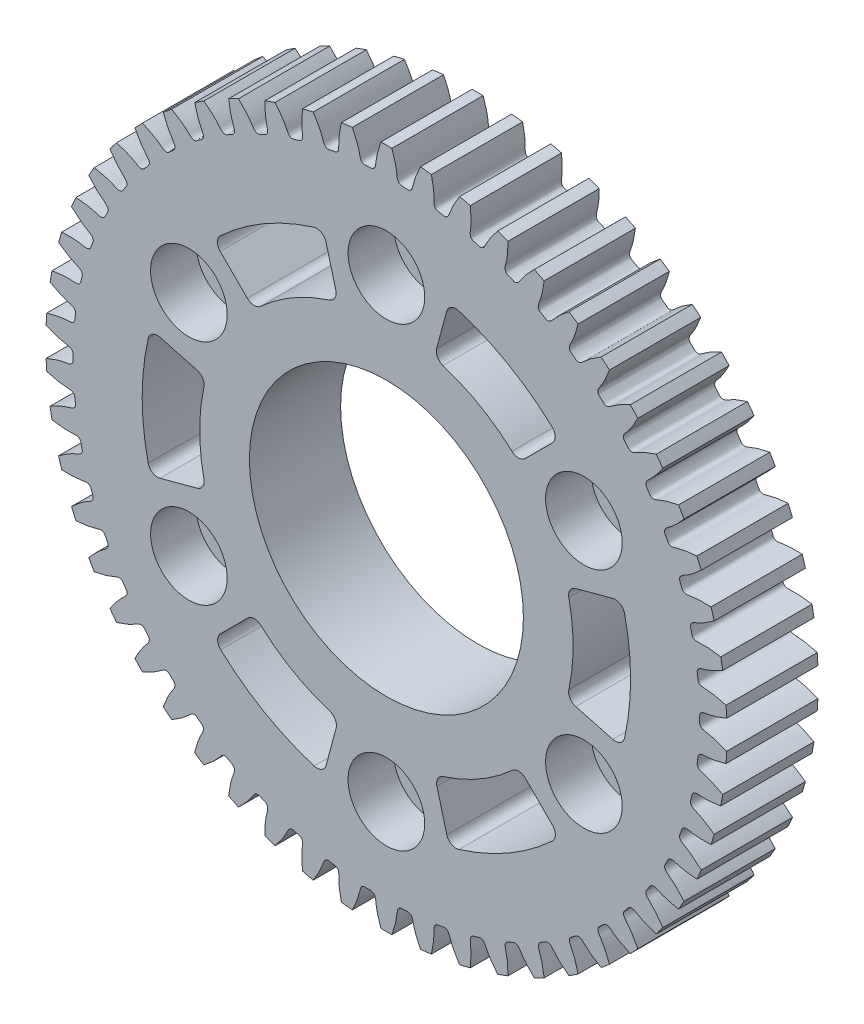
SolidWorks part; units mm, degrees
ref_plane "Front Plane" through (0, 0, 0) normal (0, 0, 1) x (1, 0, 0)
ref_plane "Top Plane" through (0, 0, 0) normal (0, 1, 0) x (1, 0, 0)
ref_plane "Right Plane" through (0, 0, 0) normal (1, 0, 0) x (0, 0, -1)
ref_plane "Plane1" through (0, 0, 4.7625) normal (0, 0, 1) x (1, 0, 0)
sketch "Sketch1" plane through (0, 0, 4.7625) normal (0, 0, 1) x (1, 0, 0)
  arc A0 (35.1151, 5.6076) -> (34.9153, 6.7406) centre (0, 0) ccw
  arc A1 (34.2266, 9.6463) -> (33.8967, 10.7484) centre (0, 0) ccw
  arc A2 (32.8753, 13.5546) -> (32.4197, 14.6109) centre (0, 0) ccw
  arc A3 (31.0794, 17.2795) -> (30.5042, 18.2758) centre (0, 0) ccw
  arc A4 (28.8633, 20.7708) -> (28.1763, 21.6936) centre (0, 0) ccw
  arc A5 (26.2568, 23.9812) -> (25.4673, 24.818) centre (0, 0) ccw
  arc A6 (23.2952, 26.8672) -> (22.4139, 27.6067) centre (0, 0) ccw
  arc A7 (20.0186, 29.39) -> (19.0574, 30.0221) centre (0, 0) ccw
  arc A8 (16.4712, 31.5153) -> (15.4432, 32.0316) centre (0, 0) ccw
  arc A9 (12.7012, 33.2144) -> (11.6201, 33.6078) centre (0, 0) ccw
  arc A10 (8.7593, 34.4643) -> (7.6399, 34.7296) centre (0, 0) ccw
  arc A11 (4.6991, 35.2482) -> (3.5564, 35.3817) centre (0, 0) ccw
  arc A12 (0.5752, 35.5553) -> (-0.5752, 35.5553) centre (0, 0) ccw
  arc A13 (-3.5564, 35.3817) -> (-4.6991, 35.2482) centre (0, 0) ccw
  arc A14 (-7.6399, 34.7296) -> (-8.7593, 34.4643) centre (0, 0) ccw
  arc A15 (-11.6201, 33.6078) -> (-12.7012, 33.2144) centre (0, 0) ccw
  arc A16 (-15.4432, 32.0316) -> (-16.4712, 31.5153) centre (0, 0) ccw
  arc A17 (-19.0574, 30.0221) -> (-20.0186, 29.39) centre (0, 0) ccw
  arc A18 (-22.4139, 27.6067) -> (-23.2952, 26.8672) centre (0, 0) ccw
  arc A19 (-25.4673, 24.818) -> (-26.2568, 23.9812) centre (0, 0) ccw
  arc A20 (-28.1763, 21.6936) -> (-28.8633, 20.7708) centre (0, 0) ccw
  arc A21 (-30.5042, 18.2758) -> (-31.0794, 17.2795) centre (0, 0) ccw
  arc A22 (-32.4197, 14.6109) -> (-32.8753, 13.5546) centre (0, 0) ccw
  arc A23 (-33.8967, 10.7484) -> (-34.2266, 9.6463) centre (0, 0) ccw
  arc A24 (-34.9153, 6.7406) -> (-35.1151, 5.6076) centre (0, 0) ccw
  arc A25 (-35.4617, 2.6416) -> (-35.5286, 1.4931) centre (0, 0) ccw
  arc A26 (-35.5286, -1.4931) -> (-35.4617, -2.6416) centre (0, 0) ccw
  arc A27 (-35.1151, -5.6076) -> (-34.9153, -6.7406) centre (0, 0) ccw
  arc A28 (-34.2266, -9.6463) -> (-33.8967, -10.7484) centre (0, 0) ccw
  arc A29 (-32.8753, -13.5546) -> (-32.4197, -14.6109) centre (0, 0) ccw
  arc A30 (-31.0794, -17.2795) -> (-30.5042, -18.2758) centre (0, 0) ccw
  arc A31 (-28.8633, -20.7708) -> (-28.1763, -21.6936) centre (0, 0) ccw
  arc A32 (-26.2568, -23.9812) -> (-25.4673, -24.818) centre (0, 0) ccw
  arc A33 (-23.2952, -26.8672) -> (-22.4139, -27.6067) centre (0, 0) ccw
  arc A34 (-20.0186, -29.39) -> (-19.0574, -30.0221) centre (0, 0) ccw
  arc A35 (-16.4712, -31.5153) -> (-15.4432, -32.0316) centre (0, 0) ccw
  arc A36 (-12.7012, -33.2144) -> (-11.6201, -33.6078) centre (0, 0) ccw
  arc A37 (-8.7593, -34.4643) -> (-7.6399, -34.7296) centre (0, 0) ccw
  arc A38 (-4.6991, -35.2482) -> (-3.5564, -35.3817) centre (0, 0) ccw
  arc A39 (-0.5752, -35.5553) -> (0.5752, -35.5553) centre (0, 0) ccw
  arc A40 (3.5564, -35.3817) -> (4.6991, -35.2482) centre (0, 0) ccw
  arc A41 (7.6399, -34.7296) -> (8.7593, -34.4643) centre (0, 0) ccw
  arc A42 (11.6201, -33.6078) -> (12.7012, -33.2144) centre (0, 0) ccw
  arc A43 (15.4432, -32.0316) -> (16.4712, -31.5153) centre (0, 0) ccw
  arc A44 (19.0574, -30.0221) -> (20.0186, -29.39) centre (0, 0) ccw
  arc A45 (22.4139, -27.6067) -> (23.2952, -26.8672) centre (0, 0) ccw
  arc A46 (25.4673, -24.818) -> (26.2568, -23.9812) centre (0, 0) ccw
  arc A47 (28.1763, -21.6936) -> (28.8633, -20.7708) centre (0, 0) ccw
  arc A48 (30.5042, -18.2758) -> (31.0794, -17.2795) centre (0, 0) ccw
  arc A49 (32.4197, -14.6109) -> (32.8753, -13.5546) centre (0, 0) ccw
  arc A50 (33.8967, -10.7484) -> (34.2266, -9.6463) centre (0, 0) ccw
  arc A51 (34.9153, -6.7406) -> (35.1151, -5.6076) centre (0, 0) ccw
  arc A52 (35.4617, -2.6416) -> (35.5286, -1.4931) centre (0, 0) ccw
  arc A53 (35.5286, 1.4931) -> (35.4617, 2.6416) centre (0, 0) ccw
  spline S0 degree 3 number of poles 69 (35.4617, 2.6416) -> (35.1151, 5.6076)
  spline S1 degree 3 number of poles 69 (34.9153, 6.7406) -> (34.2266, 9.6463)
  spline S2 degree 3 number of poles 69 (33.8967, 10.7484) -> (32.8753, 13.5546)
  spline S3 degree 3 number of poles 69 (32.4197, 14.6109) -> (31.0794, 17.2795)
  spline S4 degree 3 number of poles 69 (30.5042, 18.2758) -> (28.8633, 20.7708)
  spline S5 degree 3 number of poles 69 (28.1763, 21.6936) -> (26.2568, 23.9812)
  spline S6 degree 3 number of poles 69 (25.4673, 24.818) -> (23.2952, 26.8672)
  spline S7 degree 3 number of poles 69 (22.4139, 27.6067) -> (20.0186, 29.39)
  spline S8 degree 3 number of poles 69 (19.0574, 30.0221) -> (16.4712, 31.5153)
  spline S9 degree 3 number of poles 69 (15.4432, 32.0316) -> (12.7012, 33.2144)
  spline S10 degree 3 number of poles 69 (11.6201, 33.6078) -> (8.7593, 34.4643)
  spline S11 degree 3 number of poles 69 (7.6399, 34.7296) -> (4.6991, 35.2482)
  spline S12 degree 3 number of poles 69 (3.5564, 35.3817) -> (0.5752, 35.5553)
  spline S13 degree 3 number of poles 69 (-0.5752, 35.5553) -> (-3.5564, 35.3817)
  spline S14 degree 3 number of poles 69 (-4.6991, 35.2482) -> (-7.6399, 34.7296)
  spline S15 degree 3 number of poles 69 (-8.7593, 34.4643) -> (-11.6201, 33.6078)
  spline S16 degree 3 number of poles 69 (-12.7012, 33.2144) -> (-15.4432, 32.0316)
  spline S17 degree 3 number of poles 69 (-16.4712, 31.5153) -> (-19.0574, 30.0221)
  spline S18 degree 3 number of poles 69 (-20.0186, 29.39) -> (-22.4139, 27.6067)
  spline S19 degree 3 number of poles 69 (-23.2952, 26.8672) -> (-25.4673, 24.818)
  spline S20 degree 3 number of poles 69 (-26.2568, 23.9812) -> (-28.1763, 21.6936)
  spline S21 degree 3 number of poles 69 (-28.8633, 20.7708) -> (-30.5042, 18.2758)
  spline S22 degree 3 number of poles 69 (-31.0794, 17.2795) -> (-32.4197, 14.6109)
  spline S23 degree 3 number of poles 69 (-32.8753, 13.5546) -> (-33.8967, 10.7484)
  spline S24 degree 3 number of poles 69 (-34.2266, 9.6463) -> (-34.9153, 6.7406)
  spline S25 degree 3 number of poles 69 (-35.1151, 5.6076) -> (-35.4617, 2.6416)
  spline S26 degree 3 number of poles 69 (-35.5286, 1.4931) -> (-35.5286, -1.4931)
  spline S27 degree 3 number of poles 69 (-35.4617, -2.6416) -> (-35.1151, -5.6076)
  spline S28 degree 3 number of poles 69 (-34.9153, -6.7406) -> (-34.2266, -9.6463)
  spline S29 degree 3 number of poles 69 (-33.8967, -10.7484) -> (-32.8753, -13.5546)
  spline S30 degree 3 number of poles 69 (-32.4197, -14.6109) -> (-31.0794, -17.2795)
  spline S31 degree 3 number of poles 69 (-30.5042, -18.2758) -> (-28.8633, -20.7708)
  spline S32 degree 3 number of poles 69 (-28.1763, -21.6936) -> (-26.2568, -23.9812)
  spline S33 degree 3 number of poles 69 (-25.4673, -24.818) -> (-23.2952, -26.8672)
  spline S34 degree 3 number of poles 69 (-22.4139, -27.6067) -> (-20.0186, -29.39)
  spline S35 degree 3 number of poles 69 (-19.0574, -30.0221) -> (-16.4712, -31.5153)
  spline S36 degree 3 number of poles 69 (-15.4432, -32.0316) -> (-12.7012, -33.2144)
  spline S37 degree 3 number of poles 69 (-11.6201, -33.6078) -> (-8.7593, -34.4643)
  spline S38 degree 3 number of poles 69 (-7.6399, -34.7296) -> (-4.6991, -35.2482)
  spline S39 degree 3 number of poles 69 (-3.5564, -35.3817) -> (-0.5752, -35.5553)
  spline S40 degree 3 number of poles 69 (0.5752, -35.5553) -> (3.5564, -35.3817)
  spline S41 degree 3 number of poles 69 (4.6991, -35.2482) -> (7.6399, -34.7296)
  spline S42 degree 3 number of poles 69 (8.7593, -34.4643) -> (11.6201, -33.6078)
  spline S43 degree 3 number of poles 69 (12.7012, -33.2144) -> (15.4432, -32.0316)
  spline S44 degree 3 number of poles 69 (16.4712, -31.5153) -> (19.0574, -30.0221)
  spline S45 degree 3 number of poles 69 (20.0186, -29.39) -> (22.4139, -27.6067)
  spline S46 degree 3 number of poles 69 (23.2952, -26.8672) -> (25.4673, -24.818)
  spline S47 degree 3 number of poles 69 (26.2568, -23.9812) -> (28.1763, -21.6936)
  spline S48 degree 3 number of poles 69 (28.8633, -20.7708) -> (30.5042, -18.2758)
  spline S49 degree 3 number of poles 69 (31.0794, -17.2795) -> (32.4197, -14.6109)
  spline S50 degree 3 number of poles 69 (32.8753, -13.5546) -> (33.8967, -10.7484)
  spline S51 degree 3 number of poles 69 (34.2266, -9.6463) -> (34.9153, -6.7406)
  spline S52 degree 3 number of poles 69 (35.1151, -5.6076) -> (35.4617, -2.6416)
  spline S53 degree 3 number of poles 69 (35.5286, -1.4931) -> (35.5286, 1.4931)
extrude "Boss-Extrude1" add sketch "Sketch1" against normal blind 9.525
sketch "Sketch2" plane through (0, 0, 4.7625) normal (0, 0, 1) x (1, 0, 0)
  line L0 (-5.0224, 18.8421) -> (-6.5753, 24.6377)
  line L1 (-18.0671, 17.9953) -> (-13.8245, 13.7526)
  arc A0 (-13.8245, 13.7526) -> (-5.0224, 18.8421) centre (0, 0) cw
  arc A1 (-6.5753, 24.6377) -> (-18.0671, 17.9953) centre (0, 0) ccw
extrude "Cut-Extrude1" cut sketch "Sketch2" against normal through all
sketch "Sketch3" plane through (0, 0, 4.7625) normal (0, 0, 1) x (1, 0, 0)
  line L0 (-18.829, 5.0715) -> (-24.6245, 6.6244)
  line L1 (-24.6179, -6.6489) -> (-18.8223, -5.096)
  arc A0 (-18.8223, -5.096) -> (-18.829, 5.0715) centre (0, 0) cw
  arc A1 (-24.6245, 6.6244) -> (-24.6179, -6.6489) centre (0, 0) ccw
extrude "Cut-Extrude2" cut sketch "Sketch3" against normal through all
sketch "Sketch4" plane through (0, 0, 4.7625) normal (0, 0, 1) x (1, 0, 0)
  line L0 (-13.8065, -13.7706) -> (-18.0492, -18.0133)
  line L1 (-6.5508, -24.6442) -> (-4.9979, -18.8486)
  arc A0 (-4.9979, -18.8486) -> (-13.8065, -13.7706) centre (0, 0) cw
  arc A1 (-18.0492, -18.0133) -> (-6.5508, -24.6442) centre (0, 0) ccw
extrude "Cut-Extrude3" cut sketch "Sketch4" against normal through all
sketch "Sketch5" plane through (0, 0, 4.7625) normal (0, 0, 1) x (1, 0, 0)
  line L0 (5.0224, -18.8421) -> (6.5753, -24.6377)
  line L1 (18.0671, -17.9953) -> (13.8245, -13.7526)
  arc A0 (13.8245, -13.7526) -> (5.0224, -18.8421) centre (0, 0) cw
  arc A1 (6.5753, -24.6377) -> (18.0671, -17.9953) centre (0, 0) ccw
extrude "Cut-Extrude4" cut sketch "Sketch5" against normal through all
sketch "Sketch6" plane through (0, 0, 4.7625) normal (0, 0, 1) x (1, 0, 0)
  line L0 (13.8065, 13.7706) -> (18.0492, 18.0133)
  line L1 (6.5508, 24.6442) -> (4.9979, 18.8486)
  arc A0 (4.9979, 18.8486) -> (13.8065, 13.7706) centre (0, 0) cw
  arc A1 (18.0492, 18.0133) -> (6.5508, 24.6442) centre (0, 0) ccw
extrude "Cut-Extrude5" cut sketch "Sketch6" against normal through all
sketch "Sketch7" plane through (0, 0, -4.7625) normal (0, 0, -1) x (-1, 0, 0)
  line L0 (-24.6245, -6.6244) -> (-18.829, -5.0715)
  line L1 (-18.8223, 5.096) -> (-24.6179, 6.6489)
  arc A0 (-24.6179, 6.6489) -> (-24.6245, -6.6244) centre (0, 0) ccw
  arc A1 (-18.829, -5.0715) -> (-18.8223, 5.096) centre (0, 0) cw
extrude "Cut-Extrude6" cut sketch "Sketch7" against normal through all
hole_wizard "M25 Clearance Hole1" positions "Sketch9" profile "Sketch8" hole size "M25" standard "ANSI Metric"
sketch "Sketch9" plane through (0, 0, 4.7625) normal (0, 0, 1) x (1, 0, 0)
  point P0 (0, 0)
sketch "Sketch8" plane through (0, 0, 4.7625) normal (1, 0, 0) x (0, -1, 0)
  line L0 (0, 0) -> (0, 9.525)
  line L1 (0, 9.525) -> (14.3065, 9.525)
  line L2 (14.3065, 9.525) -> (14.3065, 0)
  line L5 (14.3065, 0) -> (0, 0)
  line L11 (0, -6.35) -> (0, 107.95) construction
  dimension "Thru Hole Dia." = 28.6131
  dimension "Thru Hole Depth" = 9.525
hole_wizard "CBORE for M4 Hex Head Machine Screw1" positions "Sketch11" profile "Sketch10" counterbore size "M4" standard "ANSI Metric"
sketch "Sketch11" plane through (0, 0, 4.7625) normal (0, 0, 1) x (1, 0, 0)
  point P0 (-20.6222, 11.9062)
  point P1 (-20.6222, -11.9063)
  point P2 (0, -23.8125)
  point P3 (20.6222, -11.9062)
  point P4 (20.6222, 11.9063)
  point P5 (0, 23.8125)
sketch "Sketch10" plane through (-20.6222, 11.9062, 4.7625) normal (1, 0, 0) x (0, -1, 0)
  line L0 (0, 0) -> (0, 9.525)
  line L1 (0, 9.525) -> (2.15, 9.525)
  line L3 (2.15, 9.525) -> (2.15, 4.7625)
  line L4 (2.15, 4.7625) -> (4, 4.7625)
  line L5 (4, 4.7625) -> (4, 0)
  line L7 (4, 0) -> (0, 0)
  line L11 (0, -6.35) -> (0, 107.95) construction
  dimension "Thru Hole Dia." = 4.3
  dimension "Thru Hole Depth" = 9.525
  dimension "C'Bore Dia." = 8
  dimension "C'Bore Depth" = 4.7625
fillet "Fillet1" radius 1 24 edges at (-18.829, 5.0715, 0) (5.0224, -18.8421, 0) (-13.8065, -13.7706, 0) (24.6245, -6.6244, 0) (-24.6245, 6.6244, 0) (18.829, -5.0715, 0) (-18.0492, -18.0133, 0) (18.8223, 5.096, 0) (6.5753, -24.6377, 0) (6.5508, 24.6442, 0) (-24.6179, -6.6489, 0) (18.0492, 18.0133, 0) (-18.8223, -5.096, 0) (4.9979, 18.8486, 0) (-6.5508, -24.6442, 0) (13.8065, 13.7706, 0) (-4.9979, -18.8486, 0) (-18.0671, 17.9953, 0) (18.0671, -17.9953, 0) (-6.5753, 24.6377, 0) (13.8245, -13.7526, 0) (-13.8245, 13.7526, 0) (24.6179, 6.6489, 0) (-5.0224, 18.8421, 0) tangent propagation no
